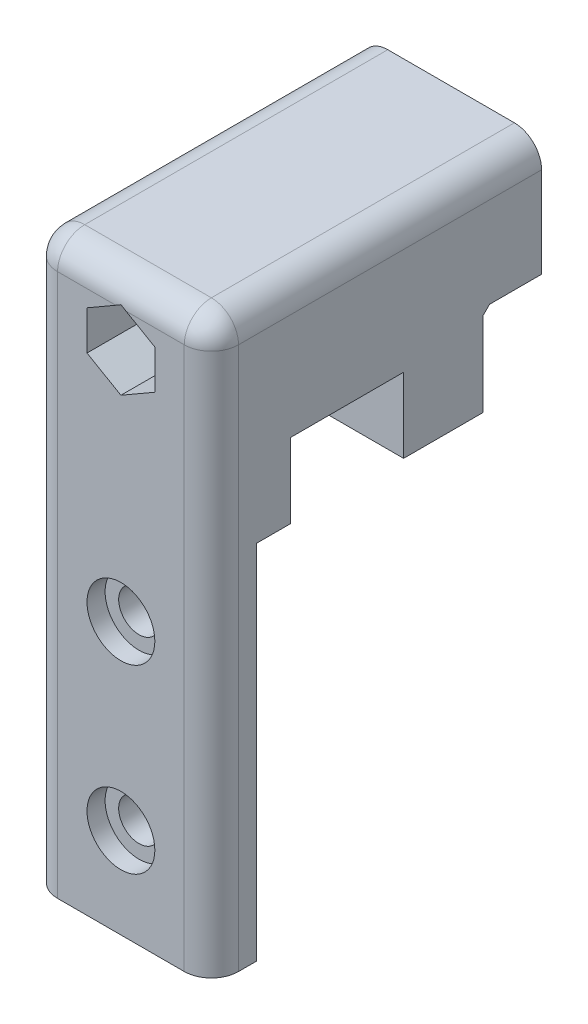
SolidWorks part; units mm, degrees
ref_plane "Front Plane" through (0, 0, 0) normal (0, 0, 1) x (1, 0, 0)
ref_plane "Top Plane" through (0, 0, 0) normal (0, 1, 0) x (1, 0, 0)
ref_plane "Right Plane" through (0, 0, 0) normal (1, 0, 0) x (0, 0, -1)
sketch "Sketch1" plane through (0, 0, 0) normal (1, 0, 0) x (0, 0, -1)
  line L1 (8.75, 0) -> (8.75, 9.25)
  line L2 (8.75, 9.25) -> (9.5, 10)
  line L3 (9.5, 10) -> (15.25, 10)
  line L4 (15.25, 10) -> (15.25, 23)
  line L5 (15.25, 23) -> (-19.25, 23)
  line L6 (-19.25, 23) -> (-19.25, -40)
  line L7 (-19.25, -40) -> (-16.25, -40)
  line L8 (-16.25, -40) -> (-16.25, 0)
  line L9 (-16.25, 0) -> (-12.5, 0)
  line L13 (0, 0) -> (3.75, 0)
  line L15 (-12.5, 0) -> (-12.25, 0) construction
  line L16 (-12.25, 0) -> (-12.25, 8) construction
  line L17 (-12.25, 8) -> (-0.25, 8) construction
  line L18 (-0.25, 8) -> (-0.25, 0) construction
  line L19 (-0.25, 0) -> (0, 0) construction
  line L20 (-12.5, 0) -> (-12.5, 8.25)
  line L21 (-12.5, 8.25) -> (0, 8.25)
  line L22 (0, 8.25) -> (0, 0)
  line L23 (8.75, 8) -> (8.75, -22) construction
  line L24 (3.75, 0) -> (8.75, 0)
  line L25 (15.25, 23) -> (15.25, 10) construction
  line L26 (15.25, 10) -> (10.75, 10) construction
  line L27 (47.75, 23) -> (15.25, 23) construction
  dimension "D3" = 12
  dimension "D4" = 8
  dimension "D1" = 20
  dimension "D5" = 225
  dimension "D6" = 0.75
  dimension "D7" = 40
  dimension "D8" = 3
  dimension "D2" = 0.25
extrude "Boss-Extrude1" add sketch "Sketch1" along normal blind 20
sketch "Sketch2" plane through (0, 0, 19.25) normal (0, 0, 1) x (1, 0, 0)
  line L0 (10, -40) -> (10, -30) construction
  line L1 (20, -40) -> (0, -40) construction
  line L2 (10, -30) -> (10, -20) construction
  line L3 (10, -20) -> (10, -10) construction
  circle A0 centre (10, -30) radius 2.25
  circle A1 centre (10, -10) radius 2 construction
  circle A2 centre (10, -10) radius 2.25
  circle A3 centre (10, 16) radius 2.25
  circle A4 centre (10, 16) radius 2.75 construction
  dimension "D2" = 4
  dimension "D1" = 10
  dimension "D3" = 0.25
extrude "Cut-Extrude1" cut sketch "Sketch2" against normal up to next
sketch "Sketch3" plane through (0, 0, 19.25) normal (0, 0, 1) x (1, 0, 0)
  line L0 (13.75, 18.1651) -> (10, 20.3301)
  line L1 (13.5, 18.0207) -> (10, 20.0415) construction
  line L2 (10, 20.0415) -> (6.5, 18.0207) construction
  line L3 (6.5, 18.0207) -> (6.5, 13.9793) construction
  line L4 (0, 23) -> (0, -40)
  line L5 (0, -40) -> (20, -40)
  line L6 (20, -40) -> (20, 23)
  line L7 (20, 23) -> (0, 23)
  line L8 (0, 23) -> (0, -40)
  line L9 (0, -40) -> (20, -40)
  line L10 (20, -40) -> (20, 23)
  line L11 (20, 23) -> (0, 23)
  line L12 (6.5, 13.9793) -> (10, 11.9585) construction
  line L13 (10, 11.9585) -> (13.5, 13.9793) construction
  line L14 (13.5, 13.9793) -> (13.5, 18.0207) construction
  line L15 (10, 20.3301) -> (6.25, 18.1651)
  line L16 (6.25, 18.1651) -> (6.25, 13.8349)
  line L17 (6.25, 13.8349) -> (10, 11.6699)
  line L18 (10, 11.6699) -> (13.75, 13.8349)
  line L19 (13.75, 13.8349) -> (13.75, 18.1651)
  circle A0 centre (10, -10) radius 3.5 construction
  circle A1 centre (10, -30) radius 3.75
  circle A2 centre (10, -10) radius 2.25 construction
  circle A3 centre (10, -30) radius 2.25 construction
  circle A4 centre (10, -10) radius 3.75
  circle A7 centre (10, 16) radius 3.5 construction
  circle A8 centre (10, 16) radius 2.25 construction
  dimension "D2" = 0.25
  dimension "D3" = 7
  dimension "D4" = 7
  dimension "D5" = 0.25
extrude "Boss-Extrude2" add sketch "Sketch3" along normal blind 2
fillet "Fillet1" radius 3 5 edges at (0, 23, 3) (20, 23, 3) (10, 23, 21.25) (20, -8.5, 21.25) (0, -8.5, 21.25)
sketch "Sketch4" plane through (0, 0, 19.25) normal (0, 0, 1) x (1, 0, 0)
  line L6 (10, 11.6699) -> (13.75, 13.8349)
  line L7 (13.75, 13.8349) -> (13.75, 18.1651)
  line L8 (13.75, 18.1651) -> (10, 20.3301)
  line L9 (10, 20.3301) -> (6.25, 18.1651)
  line L10 (6.25, 18.1651) -> (6.25, 13.8349)
  line L11 (6.25, 13.8349) -> (10, 11.6699)
  line L12 (10, 11.6699) -> (13.75, 13.8349)
  line L13 (13.75, 13.8349) -> (13.75, 18.1651)
  line L14 (13.75, 18.1651) -> (10, 20.3301)
  line L15 (10, 20.3301) -> (6.25, 18.1651)
  line L16 (6.25, 18.1651) -> (6.25, 13.8349)
  line L17 (6.25, 13.8349) -> (10, 11.6699)
  dimension "D1" = 0
extrude "Cut-Extrude2" cut sketch "Sketch4" against normal blind 10
equation "\"Tolerance\" = 0.25mm"
equation "\"Pocket_Head_M5\"= 8mm"
equation "\"Pocket_Head_M4\" = 7mm"
equation "\"Pocket_Nut_M4\" = 7mm"
equation "\"Pocket_Nut_M5\"= 8mm"
equation "\"Pocket_Nut_M3\"= 5.5mm"
equation "\"Pocket_Head_M3\"= 5.5mm"
equation "\"D2@Sketch1\"=\"Tolerance\""
equation "\"D3@Sketch2\"=\"Tolerance\""
equation "\"D3@Sketch3\"=\"Pocket_Head_M4\""
equation "\"D2@Sketch3\"=\"Tolerance\""
equation "\"D4@Sketch3\"=\"Pocket_Nut_M4\""
equation "\"D5@Sketch3\"=\"Tolerance\""
